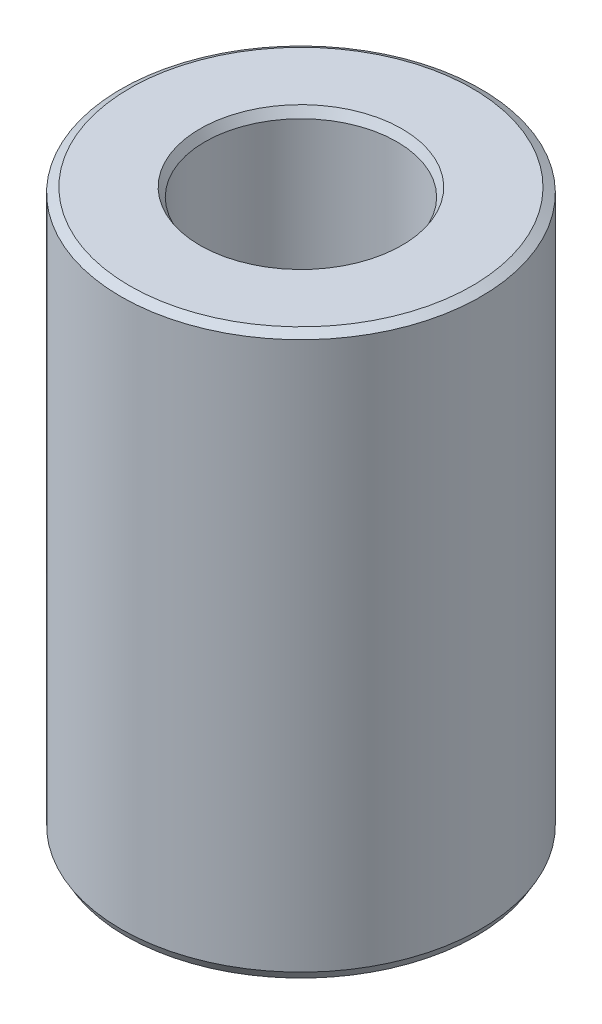
SolidWorks part; units mm, degrees
ref_plane "Front Plane" through (0, 0, 0) normal (0, 0, 1) x (1, 0, 0)
ref_plane "Top Plane" through (0, 0, 0) normal (0, 1, 0) x (1, 0, 0)
ref_plane "Right Plane" through (0, 0, 0) normal (1, 0, 0) x (0, 0, -1)
sketch "Sketch1" plane through (0, 0, 0) normal (0, 1, 0) x (1, 0, 0)
  circle A0 centre (0, 0) radius 32.5
  dimension "SLEEVE_OD" = 65
extrude "Boss-Extrude1" add sketch "Sketch1" along normal blind 101.4306
sketch "Sketch2" plane through (0, 0, 0) normal (0, 1, 0) x (1, 0, 0)
  circle A0 centre (0, 0) radius 17.3378
  dimension "BORE_D" = 34.6755
extrude "Cut-Extrude1" cut sketch "Sketch2" along normal through all
chamfer "Chamfer1" distance 0.9074 angle 60 4 edges at (0, 101.4306, 17.3378) (0, 0, 17.3378) (0, 0, 32.5) (0, 101.4306, 32.5) first distance on face at (0, 101.4306, 17.3378) first distance on face at (0, 0, 17.3378) first distance on face at (0, 101.4306, 32.5)
